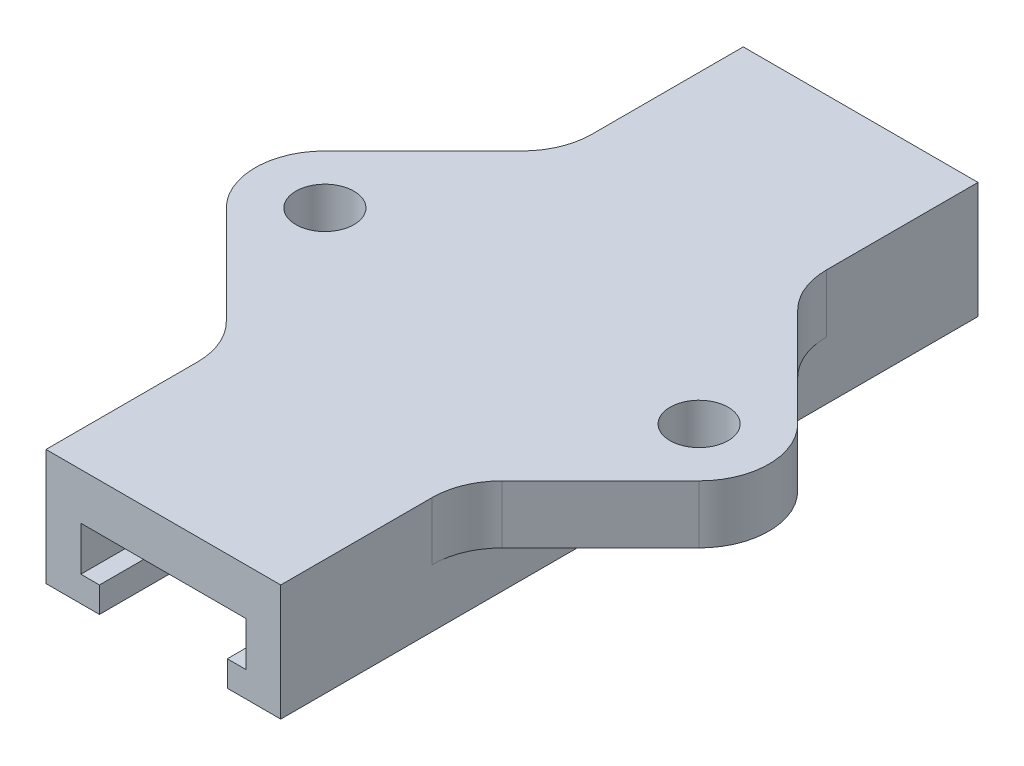
SolidWorks part; units mm, degrees
ref_plane "Front Plane" through (0, 0, 0) normal (0, 0, 1) x (1, 0, 0)
ref_plane "Top Plane" through (0, 0, 0) normal (0, 1, 0) x (1, 0, 0)
ref_plane "Right Plane" through (0, 0, 0) normal (1, 0, 0) x (0, 0, -1)
sketch "Sketch1" plane through (0, 0, 0) normal (0, 0, 1) x (1, 0, 0)
  line L0 (-12.827, 0) -> (12.827, 0)
  line L1 (12.827, 0) -> (12.827, -12.7)
  line L2 (12.827, -12.7) -> (6.985, -12.7)
  line L3 (6.985, -12.7) -> (6.985, -9.906)
  line L4 (6.985, -9.906) -> (9.017, -9.906)
  line L5 (9.017, -9.906) -> (9.017, -5.08)
  line L6 (9.017, -5.08) -> (-9.017, -5.08)
  line L7 (0, 0) -> (0, -5.08) construction
  line L8 (-9.017, -9.906) -> (-9.017, -5.08)
  line L9 (-6.985, -9.906) -> (-9.017, -9.906)
  line L10 (-6.985, -12.7) -> (-6.985, -9.906)
  line L11 (-12.827, -12.7) -> (-6.985, -12.7)
  line L12 (-12.827, 0) -> (-12.827, -12.7)
  dimension "D1" = 2.794
  dimension "D2" = 13.97
  dimension "D3" = 18.034
  dimension "D4" = 7.62
  dimension "D5" = 12.7
  dimension "D6" = 3.81
extrude "Boss-Extrude1" add sketch "Sketch1" along normal mid plane 76.2
sketch "Sketch2" plane through (0, 0, 0) normal (1, 0, 0) x (0, 0, -1)
  line L0 (-38.1, -5.08) -> (38.1, -5.08) construction
  line L1 (-38.1, -5.08) -> (38.1, -5.08) construction
  line L2 (6.858, -5.08) -> (8.7207, -7.874)
  line L3 (10.0753, -7.874) -> (11.938, -5.08)
  line L4 (11.938, -5.08) -> (6.858, -5.08)
  line L5 (9.398, -8.89) -> (9.398, -5.08) construction
  line L6 (8.7207, -7.874) -> (10.0753, -7.874)
  line L7 (8.7207, -7.874) -> (9.398, -8.89) construction
  line L8 (9.398, -8.89) -> (10.0753, -7.874) construction
  dimension "D1" = 3.81
  dimension "D2" = 5.08
  dimension "D3" = 47.498
  dimension "D4" = 2.794
extrude "Boss-Extrude2" add sketch "Sketch2" along normal mid plane 2.54 contours L3 L4 L2 L6
sketch "Sketch3" plane through (0, 0, 0) normal (0, 1, 0) x (1, 0, 0)
  line L0 (12.827, 0) -> (28.067, 0) construction
  line L1 (12.827, -38.1) -> (12.827, 38.1) construction
  line L2 (0, 38.1) -> (0, -38.1) construction
  line L3 (12.827, 38.1) -> (-12.827, 38.1) construction
  line L4 (12.827, -38.1) -> (-12.827, -38.1) construction
  line L5 (15.0588, 16.1645) -> (25.8352, 5.3882)
  line L6 (12.827, 21.5526) -> (12.827, -21.5526)
  line L7 (12.827, 21.5526) -> (12.827, 38.1) construction
  line L8 (12.827, -21.5526) -> (12.827, -38.1) construction
  line L9 (15.0588, -16.1645) -> (25.8352, -5.3882)
  line L10 (-12.827, -21.5526) -> (-12.827, -38.1) construction
  line L11 (-12.827, 21.5526) -> (-12.827, 38.1) construction
  line L12 (-12.827, 0) -> (-28.067, 0) construction
  line L13 (-15.0588, -16.1645) -> (-25.8352, -5.3882)
  line L14 (-12.827, 21.5526) -> (-12.827, -21.5526)
  line L15 (-15.0588, 16.1645) -> (-25.8352, 5.3882)
  arc A0 (25.8352, -5.3882) -> (25.8352, 5.3882) centre (20.447, 0) ccw
  arc A1 (15.0588, 16.1645) -> (12.827, 21.5526) centre (20.447, 21.5526) cw
  circle A2 centre (20.447, 0) radius 3.175
  arc A3 (15.0588, -16.1645) -> (12.827, -21.5526) centre (20.447, -21.5526) ccw
  arc A4 (-15.0588, -16.1645) -> (-12.827, -21.5526) centre (-20.447, -21.5526) cw
  circle A5 centre (-20.447, 0) radius 3.175
  arc A6 (-15.0588, 16.1645) -> (-12.827, 21.5526) centre (-20.447, 21.5526) ccw
  arc A7 (-25.8352, -5.3882) -> (-25.8352, 5.3882) centre (-20.447, 0) cw
  line M9 (-12.827, 38.1) -> (-12.827, -38.1)
  line M11 (12.827, -38.1) -> (12.827, 38.1)
  dimension "D1" = 7.62
  dimension "D2" = 6.35
  dimension "D3" = 7.62
  dimension "D4" = 7.62
  dimension "D5" = 45
extrude "Boss-Extrude3" add sketch "Sketch3" against normal blind 6.35 contours A3 L9 A0 L5 A1 A2 M11 | A7 L13 A4 A6 L15 A5 M9 region at (20.1237, 0, -10.453) region at (-20.1237, 0, 10.453)
